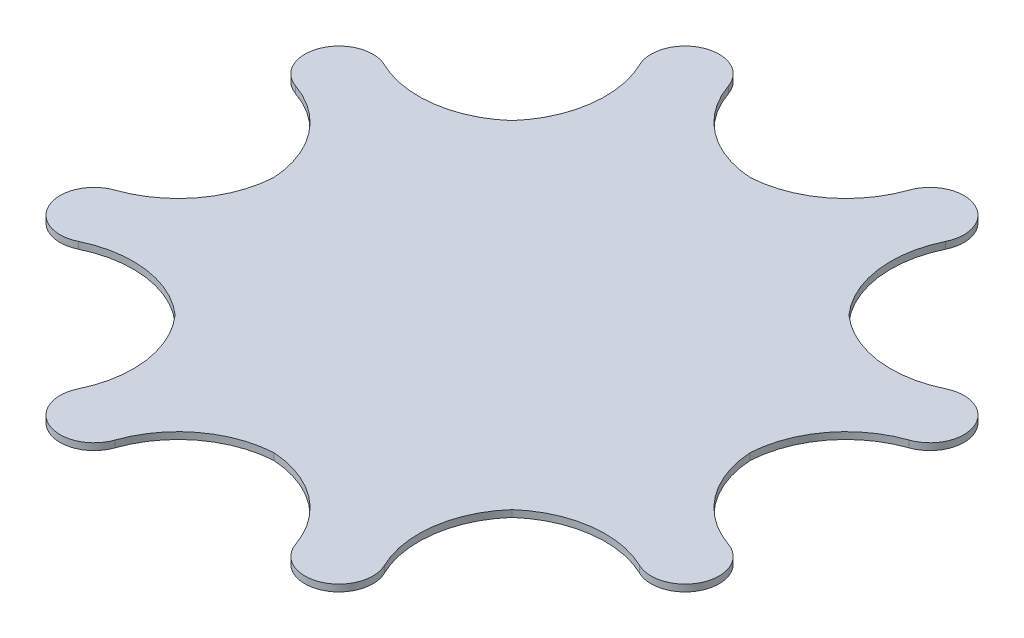
SolidWorks part; units mm, degrees
ref_plane "Front Plane" through (0, 0, 0) normal (0, 0, 1) x (1, 0, 0)
ref_plane "Top Plane" through (0, 0, 0) normal (0, 1, 0) x (1, 0, 0)
ref_plane "Right Plane" through (0, 0, 0) normal (1, 0, 0) x (0, 0, -1)
sketch "Sketch1" plane through (0, 0, 0) normal (0, 1, 0) x (1, 0, 0)
  line L0 (0, 0) -> (-36, 86.9117) construction
  line L1 (28.9949, -70) -> (70, -28.9949)
  line L2 (70, -28.9949) -> (70, 28.9949)
  line L3 (70, 28.9949) -> (28.9949, 70)
  line L4 (28.9949, 70) -> (1.7981, 70)
  line L5 (-50.7689, 48.226) -> (-70, 28.9949)
  line L6 (-70, 28.9949) -> (-70, -28.9949)
  line L7 (-70, -28.9949) -> (-28.9949, -70)
  line L8 (-28.9949, -70) -> (28.9949, -70)
  line L9 (0, 0) -> (0, 86.9117) construction
  line L10 (0, 86.9117) -> (-36, 86.9117) construction
  line L11 (-28.9949, 70) -> (-50.7689, 48.226) construction
  line L12 (1.7981, 70) -> (-28.9949, 70) construction
  circle A0 centre (0, 0) radius 70 construction
  arc A1 (-26.5505, 90.1838) -> (-44.9955, 82.5436) centre (-36, 86.9117) ccw
  arc A2 (-44.9955, 82.5436) -> (-50.7689, 48.226) centre (-71.9821, 69.4392) cw
  arc A3 (-26.5505, 90.1838) -> (1.7981, 70) centre (1.7981, 100) ccw
  arc A4 (-44.9955, 82.5436) -> (-32.1732, 77.6729) centre (-36, 86.9117) ccw construction
  arc A5 (-32.1732, 77.6729) -> (-26.5505, 90.1838) centre (-36, 86.9117) ccw construction
  dimension "D1" = 20
  dimension "D3" = 140
  dimension "D4" = 30
  dimension "D2" = 36
extrude "Boss-Extrude1" add sketch "Sketch1" along normal blind 2
ref_axis "Axis1" through (0, 2.1, 0) along (0, -1, 0)
pattern_circular "CirPattern1" count 8 over 360 about axis through (0, 2.1, 0) along (0, -1, 0) of "Boss-Extrude1"
